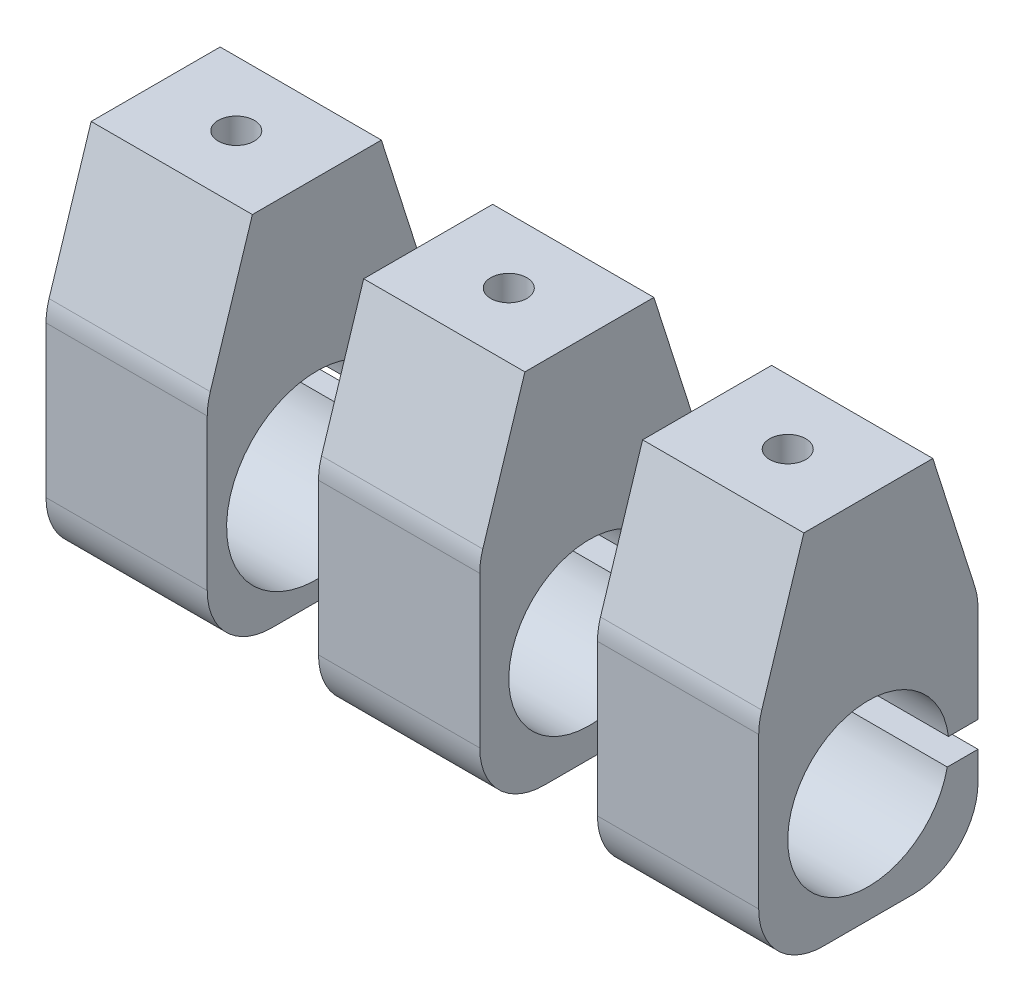
SolidWorks part; units mm, degrees
ref_plane "Front Plane" through (0, 0, 0) normal (0, 0, 1) x (1, 0, 0)
ref_plane "Top Plane" through (0, 0, 0) normal (0, 1, 0) x (1, 0, 0)
ref_plane "Right Plane" through (0, 0, 0) normal (1, 0, 0) x (0, 0, -1)
sketch "Sketch1" plane through (0, 0, 0) normal (1, 0, 0) x (0, 0, -1)
  line L0 (-10, 40) -> (10, 40)
  line L1 (10, 40) -> (17, 18)
  line L2 (17, 18) -> (17, -17)
  line L3 (17, -17) -> (-17, -17)
  line L4 (-17, -17) -> (-17, 18)
  line L5 (-17, 18) -> (-10, 40)
  line L6 (17, 1.45) -> (12.4156, 1.45)
  line L7 (17, -2.55) -> (12.2371, -2.55)
  line L9 (19, 19) -> (-19, 19) construction
  circle A0 centre (0, 0) radius 14
  circle A1 centre (0, 0) radius 12.5
  point P6 (0, 40)
  point P15 (14.6186, -2.55)
  dimension "D2" = 25
  dimension "D3" = 28
  dimension "D1" = 20
  dimension "D4" = 17
  dimension "D5" = 35
  dimension "D6" = 17
  dimension "D7" = 22
  dimension "D8" = 4
  dimension "D9" = 17.55
extrude "zoom lense mount" add sketch "Sketch1" along normal blind 25 contours L5 L4 L3 L2 L1 L0 A0 region at (0, 14.9335, 0.1637)
extrude "spec mount1" add sketch "Sketch1<4>" along normal blind 25 from offset 42.25 separate body contours A0 A1 | L5 L4 L3 L2 L1 L0 A0 region at (0, 14.9335, 0.1637) region at (0, 1.8454, -13.1702)
sketch "Sketch1<4>" plane through (0, 0, 0) normal (1, 0, 0) x (0, 0, -1) same geometry as "Sketch1"
extrude "spec mount 2" add sketch "Sketch1<5>" along normal blind 25 from offset 85.5 separate body contours L5 L4 L3 L2 L1 L0 A0 | A0 A1 region at (0, 14.9335, 0.1637) region at (0, 1.8454, -13.1702)
sketch "Sketch1<5>" plane through (0, 0, 0) normal (1, 0, 0) x (0, 0, -1) same geometry as "Sketch1"
fillet "Fillet1" radius 10 4 edges at (12.5, -17, -17) (12.5, 18, -17) (12.5, -17, 17) (12.5, 18, 17)
fillet "Fillet2" radius 10 4 edges at (54.75, -17, -17) (54.75, 18, -17) (54.75, -17, 17) (54.75, 18, 17)
fillet "Fillet3" radius 10 4 edges at (98, -17, -17) (98, 18, -17) (98, -17, 17) (98, 18, 17)
sketch "Sketch2" plane through (0, 40, 0) normal (0, 1, 0) x (1, 0, 0)
  line L0 (85.5, -10) -> (85.5, 10) construction
  circle A0 centre (98, 0) radius 2.8
  dimension "D2" = 5.6
  dimension "D1" = 12.5
extrude "Cut-Extrude1" cut sketch "Sketch2" against normal blind 30
sketch "Sketch3" plane through (0, 40, 0) normal (0, 1, 0) x (1, 0, 0)
  line L0 (67.25, -10) -> (67.25, 10) construction
  circle A0 centre (54.75, 0) radius 2.8
  dimension "D2" = 5.6
  dimension "D1" = 12.5
extrude "Cut-Extrude2" cut sketch "Sketch3" against normal blind 30
sketch "Sketch4" plane through (0, 40, 0) normal (0, 1, 0) x (1, 0, 0)
  line L0 (0, -10) -> (0, 10) construction
  circle A0 centre (12.5, 0) radius 2.8
  dimension "D2" = 5.6
  dimension "D1" = 12.5
extrude "Cut-Extrude3" cut sketch "Sketch4" against normal blind 30
